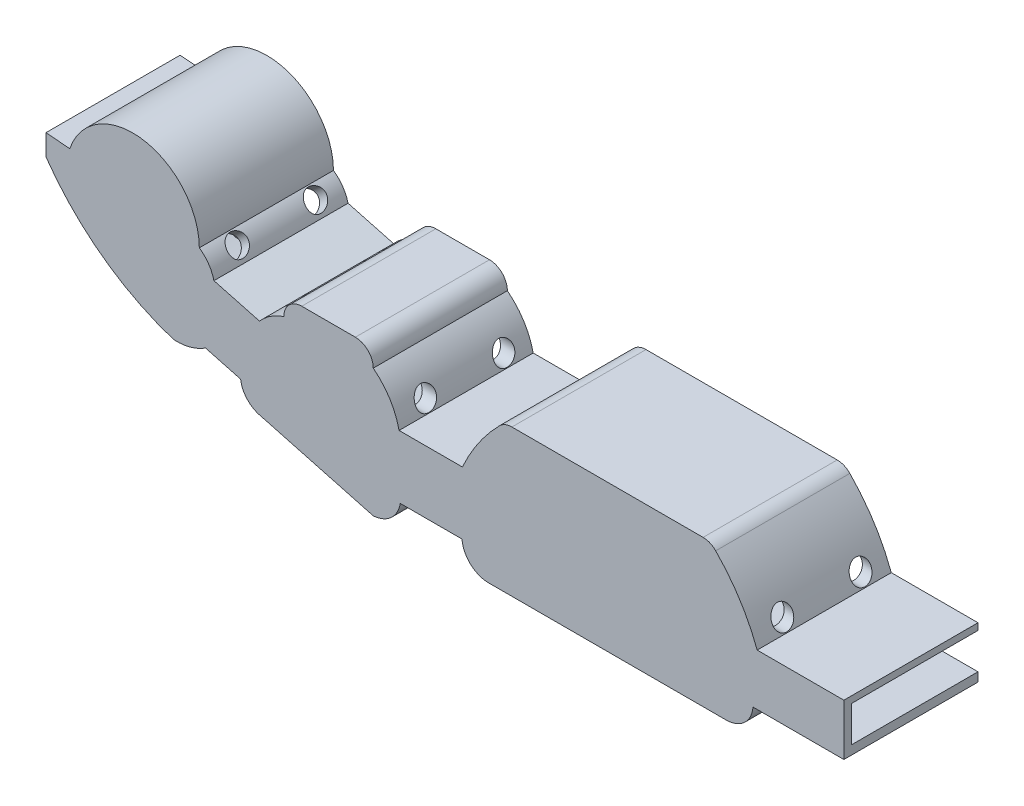
SolidWorks part; units mm, degrees
ref_plane "Front Plane" through (0, 0, 0) normal (0, 0, 1) x (1, 0, 0)
ref_plane "Top Plane" through (0, 0, 0) normal (0, 1, 0) x (1, 0, 0)
ref_plane "Right Plane" through (0, 0, 0) normal (1, 0, 0) x (0, 0, -1)
sketch "Sketch1" plane through (0, 0, 0) normal (0, 0, 1) x (1, 0, 0)
  line L5 (-97.6029, 12.3858) -> (-97.6029, 15.2174)
  line L6 (-97.6029, 15.2174) -> (-94.4145, 14.9459)
  line L10 (-35.074, 12.2681) -> (-9.4143, 12.2681)
  line L11 (-34.8319, 9.152) -> (-35.1352, 10.6577)
  line L13 (-93.5639, 9.2655) -> (-96.8614, 13.2092)
  line L14 (-96.8614, 13.2092) -> (-96.8614, 13.9453)
  line L17 (-96.8614, 13.9453) -> (-96.4758, 13.5047)
  line L19 (-51.77, 3.095) -> (-40.77, 3.095)
  line L20 (-40.7743, -2.905) -> (-51.8007, -2.905)
  line L21 (-63.3947, 10.6822) -> (-63.3108, 10.6822)
  line L22 (-67.3032, -2.5288) -> (-54.7475, -5.8983)
  line L23 (-11.1807, 10.652) -> (-11.4807, 9.152)
  line L24 (-11.4807, 9.152) -> (-11.7807, 10.652)
  line L25 (-11.7807, 10.652) -> (-12.4807, 10.652)
  line L30 (-94.818, 12.3858) -> (-96.4758, 13.5047)
  line L36 (-12.4807, 10.652) -> (-12.7807, 9.152)
  line L40 (-12.7807, 9.152) -> (-13.0807, 10.652)
  line L41 (-13.0807, 10.652) -> (-13.7547, 10.652)
  line L43 (-56.0812, 12.2025) -> (-63.2812, 12.2025)
  line L44 (-68.7563, -3.3191) -> (-53.6894, -7.3625)
  line L47 (-13.7547, 10.652) -> (-14.0547, 9.152)
  line L48 (-14.0547, 9.152) -> (-14.3547, 10.652)
  line L49 (-14.3547, 10.652) -> (-15.0547, 10.652)
  line L50 (-15.0547, 10.652) -> (-15.3547, 9.152)
  line L51 (-15.3547, 9.152) -> (-15.6547, 10.652)
  line L52 (-15.6547, 10.652) -> (-16.3547, 10.652)
  line L53 (-16.3547, 10.652) -> (-16.6547, 9.152)
  line L54 (-16.6547, 9.152) -> (-16.9547, 10.652)
  line L55 (-16.9547, 10.652) -> (-17.6547, 10.652)
  line L56 (-17.6547, 10.652) -> (-17.9547, 9.152)
  line L57 (-17.9547, 9.152) -> (-18.2547, 10.652)
  line L58 (-18.2547, 10.652) -> (-18.9547, 10.652)
  line L59 (-18.9547, 10.652) -> (-19.2547, 9.152)
  line L60 (-19.2547, 9.152) -> (-19.5547, 10.652)
  line L61 (-19.5547, 10.652) -> (-20.2547, 10.652)
  line L62 (-20.2547, 10.652) -> (-20.5547, 9.152)
  line L63 (-20.5547, 9.152) -> (-20.8547, 10.652)
  line L64 (-20.8547, 10.652) -> (-21.5547, 10.652)
  line L65 (-21.5547, 10.652) -> (-21.8547, 9.152)
  line L66 (-21.8547, 9.152) -> (-22.1547, 10.652)
  line L67 (-22.1547, 10.652) -> (-22.8547, 10.652)
  line L68 (-22.8547, 10.652) -> (-23.1547, 9.152)
  line L69 (-23.1547, 9.152) -> (-23.4547, 10.652)
  line L70 (-23.4547, 10.652) -> (-24.1547, 10.652)
  line L71 (-24.1547, 10.652) -> (-24.4547, 9.152)
  line L72 (-24.4547, 9.152) -> (-24.7547, 10.652)
  line L73 (-24.7547, 10.652) -> (-25.4547, 10.652)
  line L74 (-25.4547, 10.652) -> (-25.7547, 9.152)
  line L75 (-25.7547, 9.152) -> (-26.0547, 10.652)
  line L76 (-26.0547, 10.652) -> (-26.7547, 10.652)
  line L77 (-26.7547, 10.652) -> (-27.0547, 9.152)
  line L78 (-27.0547, 9.152) -> (-27.3547, 10.652)
  line L79 (-27.3547, 10.652) -> (-28.0547, 10.652)
  line L80 (-28.0547, 10.652) -> (-28.3547, 9.152)
  line L81 (-28.3547, 9.152) -> (-28.6547, 10.652)
  line L82 (-28.6547, 10.652) -> (-29.3547, 10.652)
  line L83 (-29.3547, 10.652) -> (-29.6547, 9.152)
  line L84 (-29.6547, 9.152) -> (-29.9547, 10.652)
  line L85 (-29.9547, 10.652) -> (-30.6547, 10.652)
  line L86 (-30.6547, 10.652) -> (-30.9547, 9.152)
  line L87 (-30.9547, 9.152) -> (-31.2547, 10.652)
  line L88 (-31.2547, 10.652) -> (-31.9547, 10.652)
  line L89 (-31.9547, 10.652) -> (-32.2547, 9.152)
  line L90 (-32.2547, 9.152) -> (-32.5547, 10.652)
  line L91 (-32.5547, 10.652) -> (-33.2547, 10.652)
  line L92 (-33.2547, 10.652) -> (-33.5547, 9.152)
  line L93 (-33.5547, 9.152) -> (-33.8547, 10.652)
  line L94 (-33.8547, 10.652) -> (-34.5287, 10.652)
  line L95 (-34.5287, 10.652) -> (-34.8319, 9.152)
  line L100 (-57.3947, 10.6822) -> (-57.5369, 10.6822)
  line L101 (-57.5369, 10.6822) -> (-57.8369, 9.1822)
  line L102 (-57.8369, 9.1822) -> (-58.1369, 10.6822)
  line L103 (-58.1369, 10.6822) -> (-58.8369, 10.6822)
  line L104 (-58.8369, 10.6822) -> (-59.1369, 9.1822)
  line L105 (-59.1369, 9.1822) -> (-59.4369, 10.6822)
  line L106 (-59.4369, 10.6822) -> (-60.1108, 10.6822)
  line L107 (-60.1108, 10.6822) -> (-60.4108, 9.1822)
  line L108 (-60.4108, 9.1822) -> (-60.7108, 10.6822)
  line L109 (-60.7108, 10.6822) -> (-61.4108, 10.6822)
  line L110 (-61.4108, 10.6822) -> (-61.7108, 9.1822)
  line L111 (-61.7108, 9.1822) -> (-62.0108, 10.6822)
  line L112 (-62.0108, 10.6822) -> (-62.7108, 10.6822)
  line L113 (-62.7108, 10.6822) -> (-63.0108, 9.1822)
  line L114 (-63.0108, 9.1822) -> (-63.3108, 10.6822)
  line L118 (-78.7208, 14.8576) -> (-79.0208, 12.8576)
  line L119 (-79.0208, 12.8576) -> (-79.3208, 15.955)
  line L120 (-80.0208, 16.8755) -> (-80.3208, 15.6755)
  line L121 (-80.3208, 15.6755) -> (-80.6208, 17.4876)
  line L122 (-81.3208, 18.0603) -> (-81.6208, 16.9603)
  line L123 (-81.6208, 16.9603) -> (-81.9208, 18.4574)
  line L124 (-82.6208, 18.8313) -> (-82.9208, 17.8313)
  line L125 (-82.9208, 17.8313) -> (-83.2208, 19.0854)
  line L126 (-83.9208, 19.313) -> (-84.2208, 18.263)
  line L127 (-84.2208, 18.263) -> (-84.5208, 19.4536)
  line L128 (-85.2208, 19.5578) -> (-85.5208, 18.4578)
  line L129 (-85.5208, 18.4578) -> (-85.8208, 19.5977)
  line L130 (-86.5221, 19.5875) -> (-86.8221, 18.3969)
  line L131 (-86.8221, 18.3969) -> (-87.1221, 19.5298)
  line L132 (-87.8199, 19.4048) -> (-88.1199, 18.1477)
  line L133 (-88.1199, 18.1477) -> (-88.4199, 19.2451)
  line L134 (-89.1193, 18.9938) -> (-89.4193, 17.6938)
  line L135 (-89.4193, 17.6938) -> (-89.7193, 18.7169)
  line L136 (-90.4175, 18.3139) -> (-90.7175, 16.8139)
  line L137 (-90.7175, 16.8139) -> (-91.0175, 17.886)
  line L138 (-91.719, 17.2662) -> (-92.019, 15.3662)
  line L139 (-92.019, 15.3662) -> (-92.319, 16.5999)
  line L148 (-68.9499, 7.6397) -> (-75.0624, 9.2801)
  line L156 (-73.89, 0.2682) -> (-76.1872, 0.8847)
  line L157 (-73.89, 0.2682) -> (-71.4824, -0.3779)
  line L161 (-76.2959, 8.3687) -> (-68.5693, 6.2951)
  line L162 (-77.4379, 2.4628) -> (-69.5973, 0.3587)
  line L163 (-50.0495, -4.105) -> (-41.7785, -4.105)
  line L164 (-50.2154, 4.295) -> (-41.7181, 4.295)
  line L165 (-37.7463, -6.2141) -> (-6.7463, -6.2141)
  line L166 (-38.1902, -7.4141) -> (-6.3025, -7.4141)
  line L167 (-22.2463, -6.2141) -> (-22.2463, -1.2141) construction
  line L168 (-40.77, 3.095) -> (-3.7183, 3.095) construction
  line L169 (-37.1454, 8.6822) -> (-3.7183, 8.6822) construction
  line L170 (-22.2442, 4.8532) -> (-22.2442, 21.169) construction
  line L171 (8.2817, 1.895) -> (-3.6348, 1.895)
  line L172 (-10.5067, 10.652) -> (-11.1807, 10.652)
  line L173 (-9.9067, 10.652) -> (-9.3532, 10.652)
  line L174 (-35.1352, 10.6577) -> (-35.1352, 4.8532) construction
  line L175 (-35.1352, 4.8532) -> (-9.3532, 4.8532) construction
  line L176 (-9.9067, 10.652) -> (-10.2067, 9.152)
  line L177 (-10.2067, 9.152) -> (-10.5067, 10.652)
  line L178 (-9.3532, 4.8532) -> (-9.3532, 10.652) construction
  line L179 (-3.7183, -2.905) -> (8.2817, -2.905)
  line L180 (-2.7142, -4.105) -> (9.4817, -4.105)
  line L183 (9.4817, 2.795) -> (9.4817, -4.105)
  line L184 (8.2817, 1.895) -> (8.2817, -2.905)
  line L185 (-2.1578, 2.795) -> (9.4817, 2.795)
  arc A2 (-93.5639, 9.2655) -> (-80.9402, 0.8179) centre (-72.8174, 26.6123) ccw
  arc A5 (-35.1352, 10.6577) -> (-36.661, 9.9746) centre (-35.1586, 8.6645) ccw
  arc A6 (-37.1454, 8.6822) -> (-40.77, 3.095) centre (-32.8748, 1.9424) ccw
  arc A8 (-36.661, 9.9746) -> (-37.1454, 8.6822) centre (-35.179, 8.6822) ccw
  arc A14 (-78.0208, 11.2299) -> (-78.7208, 14.8576) centre (-86.0539, 11.5612) ccw
  arc A15 (-79.3208, 15.955) -> (-80.0208, 16.8755) centre (-86.0539, 11.5612) ccw
  arc A16 (-80.6208, 17.4876) -> (-81.3208, 18.0603) centre (-86.0539, 11.5612) ccw
  arc A19 (-40.7743, -2.905) -> (-37.7463, -6.2141) centre (-37.7903, -3.2144) ccw
  arc A25 (-81.9208, 18.4574) -> (-82.6208, 18.8313) centre (-86.0539, 11.5612) ccw
  arc A26 (-54.7475, -5.8983) -> (-51.8007, -2.905) centre (-55.0595, -2.644) ccw
  arc A27 (-69.5973, 0.3587) -> (-67.3032, -2.5288) centre (-66.724, 0.2864) ccw
  arc A28 (-76.1872, 0.8847) -> (-80.4983, -0.2669) centre (-80.1184, 6.9561) cw
  arc A29 (-83.2208, 19.0854) -> (-83.9208, 19.313) centre (-86.0539, 11.5612) ccw
  arc A30 (-84.5208, 19.4536) -> (-85.2208, 19.5578) centre (-86.0539, 11.5612) ccw
  arc A31 (-41.7181, 4.295) -> (-36.7682, 11.551) centre (-19.1074, -5.8132) cw
  arc A33 (-85.8208, 19.5977) -> (-86.5221, 19.5875) centre (-86.0539, 11.5612) ccw
  arc A34 (-80.9402, 0.8179) -> (-77.4379, 2.4628) centre (-80.1638, 3.7157) ccw
  arc A37 (-76.2959, 8.3687) -> (-78.0208, 11.2299) centre (-80.3097, 7.8995) ccw
  arc A38 (-65.3947, 8.6822) -> (-68.5693, 6.2951) centre (-63.493, 2.8486) ccw
  arc A41 (-51.77, 3.095) -> (-55.3947, 8.6822) centre (-59.6652, 1.9424) ccw
  arc A42 (-55.3947, 8.6822) -> (-57.3947, 10.6822) centre (-57.3947, 8.6822) ccw
  arc A43 (-63.3947, 10.6822) -> (-65.3947, 8.6822) centre (-63.3947, 8.6822) ccw
  arc A45 (-94.0086, 12.7286) -> (-94.818, 12.3858) centre (-87.4925, -3.7856) ccw
  arc A47 (-35.074, 12.2681) -> (-36.7682, 11.551) centre (-35.074, 9.9085) ccw
  arc A48 (-87.1221, 19.5298) -> (-87.8199, 19.4048) centre (-86.0539, 11.5612) ccw
  arc A49 (-41.7785, -4.105) -> (-38.1902, -7.4141) centre (-38.1902, -3.8141) ccw
  arc A51 (-88.4199, 19.2451) -> (-89.1193, 18.9938) centre (-86.0539, 11.5612) ccw
  arc A52 (-89.7193, 18.7169) -> (-90.4175, 18.3139) centre (-86.0539, 11.5612) ccw
  arc A55 (-53.6894, -7.3625) -> (-50.0495, -4.105) centre (-53.9168, -3.446) ccw
  arc A56 (-71.4824, -0.3779) -> (-68.7563, -3.3191) centre (-68.0612, 0.0591) ccw
  arc A57 (-91.0175, 17.886) -> (-91.719, 17.2662) centre (-86.0539, 11.5612) ccw
  arc A58 (-97.6029, 12.3858) -> (-80.4983, -0.2669) centre (-70.1945, 31.5502) ccw
  arc A59 (-75.0624, 9.2801) -> (-77.0239, 12.1147) centre (-79.7705, 8.1183) ccw
  arc A60 (-65.6812, 9.8025) -> (-68.9499, 7.6397) centre (-63.3992, 2.8022) ccw
  arc A61 (-50.2154, 4.295) -> (-53.6812, 9.8025) centre (-59.5697, 2.2526) ccw
  arc A62 (-53.6812, 9.8025) -> (-56.0812, 12.2025) centre (-56.0812, 9.8025) ccw
  arc A63 (-63.2812, 12.2025) -> (-65.6812, 9.8025) centre (-63.2812, 9.8025) ccw
  arc A64 (-94.4145, 14.9459) -> (-77.0239, 12.1147) centre (-85.9551, 12.081) cw
  arc A65 (-92.319, 16.5999) -> (-94.0086, 12.7286) centre (-86.0539, 11.5612) ccw
  arc A66 (-2.7142, -4.105) -> (-6.3025, -7.4141) centre (-6.3025, -3.8141) cw
  arc A67 (-3.7183, -2.905) -> (-6.7463, -6.2141) centre (-6.7023, -3.2144) cw
  arc A69 (-7.343, 8.6822) -> (-9.3532, 10.652) centre (-10.3911, 7.5822) ccw
  arc A70 (-7.343, 8.6822) -> (-3.6348, 1.895) centre (-11.6135, 1.9424) cw
  arc A71 (-2.1578, 2.795) -> (-7.7202, 11.551) centre (-25.381, -5.8132) ccw
  arc A72 (-9.4143, 12.2681) -> (-7.7202, 11.551) centre (-9.4143, 9.9085) cw
  point P92 (-21.3666, 12.2681)
  dimension "D1" = 6
  dimension "D4" = 6
  dimension "D2" = 1.2
  dimension "D3" = 1.2
  dimension "D5" = 1.2
  dimension "D6" = 1.2
  dimension "D7" = 1.2
  dimension "D8" = 11
  dimension "D9" = 8
  dimension "D10" = 18.0933
  dimension "D11" = 20.0133
  dimension "D12" = 31
  dimension "D13" = 3.6247
  dimension "D14" = 12
  dimension "D15" = 5
  dimension "D16" = 5.6348
  dimension "D17" = 5.6348
  dimension "D18" = 4.8
  dimension "D19" = 6.9
  dimension "D20" = 11.9164
  dimension "D21" = 11.0264
  dimension "D22" = 8.1181
extrude "Walls" add sketch "Sketch1" along normal blind 16 contours A59 A64 L6 L5 A58 A28 A56 L44 A55 A49 L10 A47 A31 A61 A62 L43 A63 A60 A45 A37 A38 A43 A42 A41 L19 A6 region at (-96.495, 13.8016, 0)
sketch "Sketch2" plane through (0, 0, 0) normal (0, 0, -1) x (-1, 0, 0)
  line L10 (75.0624, 9.2801) -> (68.9499, 7.6397)
  line L11 (75.0624, 9.2801) -> (68.9499, 7.6397)
  line L12 (71.4824, -0.3779) -> (76.1872, 0.8847)
  line L13 (71.4824, -0.3779) -> (76.1872, 0.8847)
  line L14 (63.2812, 12.2025) -> (56.0812, 12.2025)
  line L15 (2.1578, 2.795) -> (-9.4817, 2.795)
  line L16 (35.074, 12.2681) -> (9.4143, 12.2681)
  line L17 (2.1578, 2.795) -> (-9.4817, 2.795)
  line L18 (-9.4817, 2.795) -> (-9.4817, -4.105)
  line L19 (53.6894, -7.3625) -> (68.7563, -3.3191)
  line L22 (97.6029, 12.3858) -> (97.6029, 15.2174)
  line L23 (97.6029, 15.2174) -> (94.4145, 14.9459)
  line L26 (63.2812, 12.2025) -> (56.0812, 12.2025)
  line L28 (35.074, 12.2681) -> (9.4143, 12.2681)
  line L31 (53.6894, -7.3625) -> (68.7563, -3.3191)
  line L34 (97.6029, 12.3858) -> (97.6029, 15.2174)
  line L35 (97.6029, 15.2174) -> (94.4145, 14.9459)
  line L37 (-9.4817, 2.795) -> (-9.4817, -4.105)
  line L38 (-9.4817, -4.105) -> (2.7142, -4.105)
  line L39 (-9.4817, -4.105) -> (2.7142, -4.105)
  line L40 (6.3025, -7.4141) -> (38.1902, -7.4141)
  line L41 (6.3025, -7.4141) -> (38.1902, -7.4141)
  line L42 (41.7785, -4.105) -> (50.0495, -4.105)
  line L43 (41.7785, -4.105) -> (50.0495, -4.105)
  line L44 (50.2154, 4.295) -> (41.7181, 4.295)
  line L45 (50.2154, 4.295) -> (41.7181, 4.295)
  arc A16 (9.4143, 12.2681) -> (7.7202, 11.551) centre (9.4143, 9.9085) ccw
  arc A17 (9.4143, 12.2681) -> (7.7202, 11.551) centre (9.4143, 9.9085) ccw
  arc A18 (77.0239, 12.1147) -> (75.0624, 9.2801) centre (79.7705, 8.1183) ccw
  arc A19 (68.9499, 7.6397) -> (65.6812, 9.8025) centre (63.3992, 2.8022) ccw
  arc A20 (65.6812, 9.8025) -> (63.2812, 12.2025) centre (63.2812, 9.8025) ccw
  arc A21 (56.0812, 12.2025) -> (53.6812, 9.8025) centre (56.0812, 9.8025) ccw
  arc A22 (53.6812, 9.8025) -> (50.2154, 4.295) centre (59.5697, 2.2526) ccw
  arc A23 (41.7181, 4.295) -> (36.7682, 11.551) centre (19.1074, -5.8132) ccw
  arc A24 (36.7682, 11.551) -> (35.074, 12.2681) centre (35.074, 9.9085) ccw
  arc A25 (7.7202, 11.551) -> (2.1578, 2.795) centre (25.381, -5.8132) ccw
  arc A26 (7.7202, 11.551) -> (2.1578, 2.795) centre (25.381, -5.8132) ccw
  arc A27 (2.7142, -4.105) -> (6.3025, -7.4141) centre (6.3025, -3.8141) ccw
  arc A28 (2.7142, -4.105) -> (6.3025, -7.4141) centre (6.3025, -3.8141) ccw
  arc A30 (38.1902, -7.4141) -> (41.7785, -4.105) centre (38.1902, -3.8141) ccw
  arc A31 (50.0495, -4.105) -> (53.6894, -7.3625) centre (53.9168, -3.446) ccw
  arc A32 (68.7563, -3.3191) -> (71.4824, -0.3779) centre (68.0612, 0.0591) ccw
  arc A33 (76.1872, 0.8847) -> (80.4983, -0.2669) centre (80.1184, 6.9561) ccw
  arc A34 (80.4983, -0.2669) -> (97.6029, 12.3858) centre (70.1945, 31.5502) ccw
  arc A35 (94.4145, 14.9459) -> (77.0239, 12.1147) centre (85.9551, 12.081) ccw
  arc A36 (77.0239, 12.1147) -> (75.0624, 9.2801) centre (79.7705, 8.1183) ccw
  arc A37 (68.9499, 7.6397) -> (65.6812, 9.8025) centre (63.3992, 2.8022) ccw
  arc A38 (65.6812, 9.8025) -> (63.2812, 12.2025) centre (63.2812, 9.8025) ccw
  arc A39 (56.0812, 12.2025) -> (53.6812, 9.8025) centre (56.0812, 9.8025) ccw
  arc A40 (53.6812, 9.8025) -> (50.2154, 4.295) centre (59.5697, 2.2526) ccw
  arc A41 (41.7181, 4.295) -> (36.7682, 11.551) centre (19.1074, -5.8132) ccw
  arc A42 (36.7682, 11.551) -> (35.074, 12.2681) centre (35.074, 9.9085) ccw
  arc A48 (38.1902, -7.4141) -> (41.7785, -4.105) centre (38.1902, -3.8141) ccw
  arc A49 (50.0495, -4.105) -> (53.6894, -7.3625) centre (53.9168, -3.446) ccw
  arc A50 (68.7563, -3.3191) -> (71.4824, -0.3779) centre (68.0612, 0.0591) ccw
  arc A51 (76.1872, 0.8847) -> (80.4983, -0.2669) centre (80.1184, 6.9561) ccw
  arc A52 (80.4983, -0.2669) -> (97.6029, 12.3858) centre (70.1945, 31.5502) ccw
  arc A53 (94.4145, 14.9459) -> (77.0239, 12.1147) centre (85.9551, 12.081) ccw
  dimension "D1" = 0
extrude "Base" add sketch "Sketch2" along normal blind 1
sketch "Sketch3" [suppressed] plane through (0, 0, 0) normal (0, 0, 1) x (1, 0, 0)
  line L4 (-65.1711, 5.3832) -> (-63.3958, 4.9067) construction
  line L5 (-84.8697, 19.5134) -> (-85.1843, 17.3997) construction
  line L6 (-51.77, 3.095) -> (-68.5693, 3.095) construction
  line L7 (-68.5693, 6.2951) -> (-68.5693, 3.095) construction
  line L8 (-51.77, 3.095) -> (-54.6697, 3.095) construction
  line L9 (-68.5693, 6.2951) -> (-65.1711, 5.3832) construction
  line L10 (-56.4697, 3.095) -> (-54.6697, 3.095) construction
  line L11 (-80.595, 9.5224) -> (-82.2789, 9.9743)
  line L12 (-80.595, 9.5224) -> (-76.2959, 8.3687) construction
  line L13 (-91.8537, 12.2226) -> (-90.116, 11.8146)
  line L14 (-82.2789, 9.9743) -> (-90.116, 11.8146) construction
  line L15 (-40.77, 3.095) -> (-37.27, 3.095) construction
  line L16 (-3.6422, 1.595) -> (-7.1422, 1.595) construction
  line L17 (-40.77, 3.095) -> (-3.7183, 3.095) construction
  line L18 (-22.2442, 8.652) -> (-22.2442, 3.095) construction
  line L19 (-22.8547, 10.652) -> (-22.1547, 10.652) construction
  line L20 (-22.2442, 10.652) -> (-22.2442, 8.652) construction
  line L21 (-37.27, 3.095) -> (-34.1769, 3.095) construction
  line L22 (-11.7175, 3.095) -> (-7.1422, 1.595) construction
  arc A1 (-82.2789, 9.9743) -> (-90.116, 11.8146) centre (-86.0365, 11.58) ccw
  arc A2 (-91.8537, 12.2226) -> (-80.595, 9.5224) centre (-86.0443, 11.6231) cw
  arc A3 (-54.6697, 3.095) -> (-65.1711, 5.3832) centre (-60.1697, 3.095) ccw construction
  arc A4 (-84.5208, 19.4536) -> (-85.2208, 19.5578) centre (-86.0539, 11.5612) ccw construction
  arc A5 (-56.4697, 3.095) -> (-63.3958, 4.9067) centre (-60.1697, 3.095) ccw construction
  arc A6 (-3.6422, 1.595) -> (-7.343, 8.6822) centre (-11.6135, 1.9424) ccw construction
  arc A7 (-7.1422, 1.595) -> (-37.27, 3.095) centre (-22.9472, -12.5401) ccw construction
  arc A8 (-11.7175, 3.095) -> (-34.1769, 3.095) centre (-22.9472, -12.5401) ccw construction
  dimension "D1" = 11
  dimension "D2" = 2.137
  dimension "D3" = 7.4
  dimension "D8" = 38.5
  dimension "D4" = 3.5184
  dimension "D5" = 3.5
  dimension "D6" = 3.5
  dimension "D7" = 2
sketch "Sketch4" [suppressed] plane through (0, 0, 16) normal (0, 0, 1) x (1, 0, 0)
  line L7 (-69.5947, 0.3005) -> (-71.4824, -0.3779)
  line L10 (-71.4824, -0.3779) -> (-76.1872, 0.8847)
  line L11 (-76.1872, 0.8847) -> (-77.6773, 2.0433)
  line L12 (-40.77, 3.095) -> (-41.1043, 4.1128)
  line L13 (-41.1043, 4.1128) -> (-49.5364, 4.1128)
  line L16 (-67.7226, 6.3478) -> (-68.9499, 7.6397)
  line L17 (-68.9499, 7.6397) -> (-75.0624, 9.2801)
  line L18 (-75.0624, 9.2801) -> (-76.3177, 7.7352)
  line L19 (-49.5364, 4.1128) -> (-51.77, 3.095)
  line L20 (-40.7743, -2.905) -> (-41.0926, -4.1129)
  line L21 (-41.0926, -4.1129) -> (-49.3636, -4.1129)
  line L22 (-49.3636, -4.1129) -> (-51.8007, -2.905)
  arc A0 (-67.7226, 6.3478) -> (-76.3177, 7.7352) centre (-69.7742, 20.955) cw
  arc A1 (-69.5947, 0.3005) -> (-77.6773, 2.0433) centre (-76.3689, -11.5028) ccw
  arc A2 (-40.7743, -2.905) -> (-51.8007, -2.905) centre (-46.2875, -28.5004) ccw
  arc A3 (-40.77, 3.095) -> (-51.77, 3.095) centre (-46.27, 28.5687) cw
extrude "Joint Width" [suppressed] add sketch "Sketch4" against normal blind 16
ref_plane "SideAnchorPlane" through (0, 0, 2.5) normal (0, 0, 1) x (1, 0, 0)
ref_plane "CentralAnchorPlane" through (0, 0, 13) normal (0, 0, 1) x (1, 0, 0)
sketch "Sketch5" [suppressed] plane through (0, 0, 3) normal (0, 0, 1) x (1, 0, 0)
  line L0 (-76.2959, 8.3687) -> (-68.5693, 6.2951) construction
  line L1 (-76.592, 9.4835) -> (-67.8744, 7.144) construction
  line L2 (-77.4258, 10.7304) -> (-66.9487, 7.9187) construction
  line L3 (-76.592, 9.4835) -> (-88.7757, 4.7797)
  line L4 (-77.4258, 10.7304) -> (-90.1205, 5.8293)
  line L5 (-78.0158, 11.7317) -> (-91.096, 6.6818)
  line L6 (-76.2959, 8.3687) -> (-87.6359, 3.9906)
  line L7 (-78.0158, 11.7317) -> (-77.4258, 10.7304)
  line L9 (-76.592, 9.4835) -> (-76.0479, 8.9395)
  line L10 (-76.0479, 8.9395) -> (-76.2959, 8.3687)
  line L11 (-91.096, 6.6818) -> (-91.096, 6.0024)
  line L12 (-91.096, 6.0024) -> (-90.1205, 5.8293)
  line L13 (-88.7757, 4.7797) -> (-88.5883, 3.9906)
  line L14 (-88.5883, 3.9906) -> (-87.6359, 3.9906)
  arc A0 (-76.2959, 8.3687) -> (-78.0208, 11.2299) centre (-80.3097, 7.8995) ccw construction
  arc A1 (-65.3947, 8.6822) -> (-68.5693, 6.2951) centre (-63.493, 2.8486) ccw construction
  arc A2 (-76.2959, 8.3687) -> (-78.0208, 11.2299) centre (-80.3097, 7.8995) ccw construction
  arc A4 (-93.5639, 9.2655) -> (-80.9402, 0.8179) centre (-72.8174, 26.6123) ccw construction
  arc A5 (-93.5639, 9.2655) -> (-80.9402, 0.8179) centre (-72.8174, 26.6123) ccw construction
  dimension "D1" = 1
  dimension "D2" = 1.5
  dimension "D3" = 1.1466
  dimension "D4" = 1.1466
extrude "Boss-Extrude2" [suppressed] add sketch "Sketch5" along normal blind 1 and the other way blind 1 separate body
sketch "Sketch6" [suppressed] plane through (0, 0, 4) normal (0, 0, 1) x (1, 0, 0)
  line L1 (-87.6359, 3.9906) -> (-76.2959, 8.3687)
  line L4 (-78.0158, 11.7317) -> (-91.096, 6.6818)
  line L5 (-91.096, 6.6818) -> (-91.7792, 6.284)
  line L6 (-91.7792, 6.284) -> (-88.4163, 3.7031)
  line L7 (-88.4163, 3.7031) -> (-87.6359, 3.9906)
  line L8 (-78.0158, 11.7317) -> (-75.9969, 10.8669)
  line L9 (-75.9969, 10.8669) -> (-76.2959, 8.3687)
  arc A0 (-93.5639, 9.2655) -> (-80.9402, 0.8179) centre (-72.8174, 26.6123) ccw construction
extrude "Boss-Extrude4" [suppressed] add sketch "Sketch6" along normal blind 1
sketch "Sketch7" [suppressed] plane through (0, 0, 2) normal (0, 0, -1) x (-1, 0, 0)
  line L0 (87.6359, 3.9906) -> (90.1015, 4.9746)
  line L1 (90.1015, 4.9746) -> (91.096, 6.6818)
  line L2 (91.096, 6.6818) -> (78.0158, 11.7317)
  line L3 (78.0158, 11.7317) -> (76.2959, 10.4542)
  line L4 (76.2959, 10.4542) -> (76.2959, 8.3687)
  line L5 (76.2959, 8.3687) -> (87.6359, 3.9906)
extrude "Boss-Extrude5" [suppressed] add sketch "Sketch7" along normal blind 1
extrude "Boss-Extrude6" [suppressed] add sketch "Sketch3" along normal up to surface (16 mm away)
sketch "Sketch8" plane through (0, 0, 2.5) normal (0, 0, 1) x (1, 0, 0)
  line L2 (-75.9174, 11.0626) -> (-66.0659, 8.4188) construction
  line L5 (-52.6781, 5.795) -> (-39.8619, 5.795) construction
  line L7 (-3.9894, 4.295) -> (11.6619, 4.295) construction
  line L121 (-77.8002, 11.067) -> (-76.41, 8.9592)
  line L122 (-76.7997, 11.9511) -> (-75.2827, 11.509)
  line L123 (-75.2827, 11.509) -> (-75.2827, 9.9554)
  line L124 (-75.9174, 11.0626) -> (-72.3901, 7.0708) construction
  line L138 (-66.0659, 8.4188) -> (-52.6781, 5.795) construction
  line L139 (-39.8619, 5.795) -> (-3.9894, 4.295) construction
  line L140 (-75.9174, 11.0626) -> (-76.9521, 10.1483) construction
  line L142 (-76.7997, 11.9511) -> (-77.8002, 11.067)
  line L144 (-75.2827, 9.9554) -> (-76.41, 8.9592)
  arc A2 (-75.0624, 9.2801) -> (-77.0239, 12.1147) centre (-79.7705, 8.1183) ccw construction
  circle A48 centre (-76.4347, 10.6055) radius 1.25 construction
  dimension "D22" = 2.5
ref_plane "Plane3" through (-55, 0, 0) normal (1, 0, 0) x (0, 0, -1)
sketch "Sketch14" plane through (-55, 0, 0) normal (1, 0, 0) x (0, 0, -1)
  line L0 (-13, 0.165) -> (-13, -0.165) construction
  line L1 (-2.5, 0.165) -> (-2.5, -0.165) construction
  line L2 (-16, 3.095) -> (0, 3.095) construction
  line L3 (-16, 3.095) -> (0, 3.095) construction
  line L4 (0, 3.095) -> (0, 8.4472) construction
  line L5 (0, 8.6822) -> (0, 3.095) construction
  line L6 (0, 8.4472) -> (-16, 8.4472) construction
  line L7 (-16, 8.6822) -> (-16, 3.095) construction
  line L8 (-16, 8.4472) -> (-16, 3.095) construction
  line L9 (0, 5.7711) -> (-16, 5.7711) construction
  circle A0 centre (-13, 5.7711) radius 1.4
  circle A1 centre (-2.5, 5.7711) radius 1.4
  dimension "D1" = 2.8
  dimension "D2" = 2.8
  dimension "D3" = 2.6761
  dimension "D4" = 2.6761
extrude "Cut-Extrude2" cut sketch "Sketch14" along normal up to surface (15.1249 mm away) up to face at (-39.2631, 6.0868, 8)
sketch "Sketch15" plane through (0, 0, 0) normal (1, 0, 0) x (0, 0, -1)
  line L0 (-16, 2.795) -> (1, 2.795) construction
  line L1 (-13, 2.795) -> (-13, 4.295) construction
  line L2 (-13, 14.1985) -> (-13, -14.1985) construction
  line L3 (-13, 4.295) -> (-2.5, 4.295) construction
  line L4 (-2.5, 5.795) -> (-2.5, 4.295) construction
  circle A0 centre (-13, 4.295) radius 1.4
  circle A1 centre (-2.5, 4.295) radius 1.4
  dimension "D2" = 2.8
  dimension "D1" = 1.5
extrude "Cut-Extrude3" cut sketch "Sketch15" against normal up to surface (3.9894 mm away) up to face at (-5.0502, 5.5283, 8)
ref_plane "Plane4" through (-39.5082, -33.1252, 0) normal (0.7663, 0.6425, 0) x (0, 0, -1)
sketch "Sketch16" plane through (-39.5082, -33.1252, 0) normal (0.7663, 0.6425, 0) x (0, 0, -1)
  line L0 (-2.5, 58.4664) -> (-2.5, 55.9581) construction
  line L1 (-2.5, 57.2123) -> (-13, 57.2123) construction
  line L2 (-13, 14.1985) -> (-13, -14.1985) construction
  line L3 (-16, 58.7705) -> (-16, 55.4322) construction
  line L4 (-16, 55.4322) -> (1, 55.4322) construction
  line L5 (1, 55.3382) -> (1, 58.7705) construction
  line L6 (1, 55.4322) -> (1, 58.7705) construction
  circle A0 centre (-2.5, 57.2123) radius 1.4
  circle A1 centre (-13, 57.2123) radius 1.4
  dimension "D1" = 2.8
  dimension "D2" = 3
extrude "Cut-Extrude4" cut sketch "Sketch16" against normal up to surface and the other way up to surface up to face at (-89.5671, 5.3613, 7.5) other way up to face at (-75.913, 10.7875, 7.5)
ref_plane "Plane5" through (-63.3247, 23.0762, 0) normal (-0.9396, 0.3424, 0) x (0, 0, -1)
sketch "Sketch18" plane through (-63.3247, 23.0762, 0) normal (-0.9396, 0.3424, 0) x (0, 0, -1)
  line L0 (-13, 14.8654) -> (-2.5, 14.8554) construction
  line L2 (-2.5, 14.71) -> (-2.5, 12.5914) construction
  line L3 (-2.5, 13.2814) -> (-13, 13.2814) construction
  line L4 (-13, 14.1985) -> (-13, -14.1985) construction
  line L8 (-13, 13.2814) -> (-13, 16.4494) construction
  line L9 (-13, 16.4494) -> (-2.5, 16.4294) construction
  line L10 (-2.5, 15.599) -> (-2.5, 18.1418) construction
  line L11 (-16, 16.4294) -> (1, 16.4294) construction
  line L12 (-2.5, 16.4294) -> (-2.5, 13.2814) construction
  circle A0 centre (-2.5, 14.8554) radius 1.4
  circle A1 centre (-13, 14.8654) radius 1.4
  dimension "D1" = 2.8
extrude "Cut-Extrude5" cut sketch "Sketch18" against normal up to surface (1.3116 mm away) up to face at (-67.0813, 7.6207, 8)
sketch "Sketch19" plane through (0, 0, 0) normal (0, 0, 1) x (1, 0, 0)
  line L3 (-34.8319, 9.152) -> (-35.1352, 10.6577)
  line L4 (-93.5639, 9.2655) -> (-96.8614, 13.2092)
  line L5 (-96.8614, 13.2092) -> (-96.8614, 13.9453)
  line L6 (-96.8614, 13.9453) -> (-96.4758, 13.5047)
  line L7 (-51.77, 3.095) -> (-40.77, 3.095)
  line L8 (-40.7743, -2.905) -> (-51.8007, -2.905)
  line L9 (-63.3947, 10.6822) -> (-63.3108, 10.6822)
  line L10 (-67.3032, -2.5288) -> (-54.7475, -5.8983)
  line L11 (-11.1807, 10.652) -> (-11.4807, 9.152)
  line L12 (-11.4807, 9.152) -> (-11.7807, 10.652)
  line L13 (-11.7807, 10.652) -> (-12.4807, 10.652)
  line L14 (-94.818, 12.3858) -> (-96.4758, 13.5047)
  line L15 (-12.4807, 10.652) -> (-12.7807, 9.152)
  line L16 (-12.7807, 9.152) -> (-13.0807, 10.652)
  line L17 (-13.0807, 10.652) -> (-13.7547, 10.652)
  line L20 (-13.7547, 10.652) -> (-14.0547, 9.152)
  line L21 (-14.0547, 9.152) -> (-14.3547, 10.652)
  line L22 (-14.3547, 10.652) -> (-15.0547, 10.652)
  line L23 (-15.0547, 10.652) -> (-15.3547, 9.152)
  line L24 (-15.3547, 9.152) -> (-15.6547, 10.652)
  line L25 (-15.6547, 10.652) -> (-16.3547, 10.652)
  line L26 (-16.3547, 10.652) -> (-16.6547, 9.152)
  line L27 (-16.6547, 9.152) -> (-16.9547, 10.652)
  line L28 (-16.9547, 10.652) -> (-17.6547, 10.652)
  line L29 (-17.6547, 10.652) -> (-17.9547, 9.152)
  line L30 (-17.9547, 9.152) -> (-18.2547, 10.652)
  line L31 (-18.2547, 10.652) -> (-18.9547, 10.652)
  line L32 (-18.9547, 10.652) -> (-19.2547, 9.152)
  line L33 (-19.2547, 9.152) -> (-19.5547, 10.652)
  line L34 (-19.5547, 10.652) -> (-20.2547, 10.652)
  line L35 (-20.2547, 10.652) -> (-20.5547, 9.152)
  line L36 (-20.5547, 9.152) -> (-20.8547, 10.652)
  line L37 (-20.8547, 10.652) -> (-21.5547, 10.652)
  line L38 (-21.5547, 10.652) -> (-21.8547, 9.152)
  line L39 (-21.8547, 9.152) -> (-22.1547, 10.652)
  line L40 (-22.1547, 10.652) -> (-22.8547, 10.652)
  line L41 (-22.8547, 10.652) -> (-23.1547, 9.152)
  line L42 (-23.1547, 9.152) -> (-23.4547, 10.652)
  line L43 (-23.4547, 10.652) -> (-24.1547, 10.652)
  line L44 (-24.1547, 10.652) -> (-24.4547, 9.152)
  line L45 (-24.4547, 9.152) -> (-24.7547, 10.652)
  line L46 (-24.7547, 10.652) -> (-25.4547, 10.652)
  line L47 (-25.4547, 10.652) -> (-25.7547, 9.152)
  line L48 (-25.7547, 9.152) -> (-26.0547, 10.652)
  line L49 (-26.0547, 10.652) -> (-26.7547, 10.652)
  line L50 (-26.7547, 10.652) -> (-27.0547, 9.152)
  line L51 (-27.0547, 9.152) -> (-27.3547, 10.652)
  line L52 (-27.3547, 10.652) -> (-28.0547, 10.652)
  line L53 (-28.0547, 10.652) -> (-28.3547, 9.152)
  line L54 (-28.3547, 9.152) -> (-28.6547, 10.652)
  line L55 (-28.6547, 10.652) -> (-29.3547, 10.652)
  line L56 (-29.3547, 10.652) -> (-29.6547, 9.152)
  line L57 (-29.6547, 9.152) -> (-29.9547, 10.652)
  line L58 (-29.9547, 10.652) -> (-30.6547, 10.652)
  line L59 (-30.6547, 10.652) -> (-30.9547, 9.152)
  line L60 (-30.9547, 9.152) -> (-31.2547, 10.652)
  line L61 (-31.2547, 10.652) -> (-31.9547, 10.652)
  line L62 (-31.9547, 10.652) -> (-32.2547, 9.152)
  line L63 (-32.2547, 9.152) -> (-32.5547, 10.652)
  line L64 (-32.5547, 10.652) -> (-33.2547, 10.652)
  line L65 (-33.2547, 10.652) -> (-33.5547, 9.152)
  line L66 (-33.5547, 9.152) -> (-33.8547, 10.652)
  line L67 (-33.8547, 10.652) -> (-34.5287, 10.652)
  line L68 (-34.5287, 10.652) -> (-34.8319, 9.152)
  line L69 (-57.3947, 10.6822) -> (-57.5369, 10.6822)
  line L70 (-57.5369, 10.6822) -> (-57.8369, 9.1822)
  line L71 (-57.8369, 9.1822) -> (-58.1369, 10.6822)
  line L72 (-58.1369, 10.6822) -> (-58.8369, 10.6822)
  line L73 (-58.8369, 10.6822) -> (-59.1369, 9.1822)
  line L74 (-59.1369, 9.1822) -> (-59.4369, 10.6822)
  line L75 (-59.4369, 10.6822) -> (-60.1108, 10.6822)
  line L76 (-60.1108, 10.6822) -> (-60.4108, 9.1822)
  line L77 (-60.4108, 9.1822) -> (-60.7108, 10.6822)
  line L78 (-60.7108, 10.6822) -> (-61.4108, 10.6822)
  line L79 (-61.4108, 10.6822) -> (-61.7108, 9.1822)
  line L80 (-61.7108, 9.1822) -> (-62.0108, 10.6822)
  line L81 (-62.0108, 10.6822) -> (-62.7108, 10.6822)
  line L82 (-62.7108, 10.6822) -> (-63.0108, 9.1822)
  line L83 (-63.0108, 9.1822) -> (-63.3108, 10.6822)
  line L84 (-78.7208, 14.8576) -> (-79.0208, 12.8576)
  line L85 (-79.0208, 12.8576) -> (-79.3208, 15.955)
  line L86 (-80.0208, 16.8755) -> (-80.3208, 15.6755)
  line L87 (-80.3208, 15.6755) -> (-80.6208, 17.4876)
  line L88 (-81.3208, 18.0603) -> (-81.6208, 16.9603)
  line L89 (-81.6208, 16.9603) -> (-81.9208, 18.4574)
  line L90 (-82.6208, 18.8313) -> (-82.9208, 17.8313)
  line L91 (-82.9208, 17.8313) -> (-83.2208, 19.0854)
  line L92 (-83.9208, 19.313) -> (-84.2208, 18.263)
  line L93 (-84.2208, 18.263) -> (-84.5208, 19.4536)
  line L94 (-85.2208, 19.5578) -> (-85.5208, 18.4578)
  line L95 (-85.5208, 18.4578) -> (-85.8208, 19.5977)
  line L96 (-86.5221, 19.5875) -> (-86.8221, 18.3969)
  line L97 (-86.8221, 18.3969) -> (-87.1221, 19.5298)
  line L98 (-87.8199, 19.4048) -> (-88.1199, 18.1477)
  line L99 (-88.1199, 18.1477) -> (-88.4199, 19.2451)
  line L100 (-89.1193, 18.9938) -> (-89.4193, 17.6938)
  line L101 (-89.4193, 17.6938) -> (-89.7193, 18.7169)
  line L102 (-90.4175, 18.3139) -> (-90.7175, 16.8139)
  line L103 (-90.7175, 16.8139) -> (-91.0175, 17.886)
  line L104 (-91.719, 17.2662) -> (-92.019, 15.3662)
  line L105 (-92.019, 15.3662) -> (-92.319, 16.5999)
  line L109 (-76.2959, 8.3687) -> (-68.5693, 6.2951)
  line L110 (-77.4379, 2.4628) -> (-69.5973, 0.3587)
  line L113 (-37.7463, -6.2141) -> (-6.7463, -6.2141)
  line L115 (-22.2463, -6.2141) -> (-22.2463, -1.2141) construction
  line L116 (-40.77, 3.095) -> (-3.7183, 3.095) construction
  line L117 (-37.1454, 8.6822) -> (-3.7183, 8.6822) construction
  line L118 (-22.2442, 4.8532) -> (-22.2442, 21.169) construction
  line L119 (8.2817, 1.895) -> (-3.6348, 1.895)
  line L120 (-10.5067, 10.652) -> (-11.1807, 10.652)
  line L121 (-9.9067, 10.652) -> (-9.3532, 10.652)
  line L122 (-35.1352, 10.6577) -> (-35.1352, 4.8532) construction
  line L123 (-35.1352, 4.8532) -> (-9.3532, 4.8532) construction
  line L124 (-9.9067, 10.652) -> (-10.2067, 9.152)
  line L125 (-10.2067, 9.152) -> (-10.5067, 10.652)
  line L126 (-9.3532, 4.8532) -> (-9.3532, 10.652) construction
  line L127 (-3.7183, -2.905) -> (8.2817, -2.905)
  line L130 (8.2817, 1.895) -> (8.2817, -2.905)
  arc A0 (-93.5639, 9.2655) -> (-80.9402, 0.8179) centre (-72.8174, 26.6123) ccw
  arc A1 (-35.1352, 10.6577) -> (-36.661, 9.9746) centre (-35.1586, 8.6645) ccw
  arc A2 (-37.1454, 8.6822) -> (-40.77, 3.095) centre (-32.8748, 1.9424) ccw
  arc A3 (-36.661, 9.9746) -> (-37.1454, 8.6822) centre (-35.179, 8.6822) ccw
  arc A4 (-78.0208, 11.2299) -> (-78.7208, 14.8576) centre (-86.0539, 11.5612) ccw
  arc A5 (-79.3208, 15.955) -> (-80.0208, 16.8755) centre (-86.0539, 11.5612) ccw
  arc A6 (-80.6208, 17.4876) -> (-81.3208, 18.0603) centre (-86.0539, 11.5612) ccw
  arc A7 (-40.7743, -2.905) -> (-37.7463, -6.2141) centre (-37.7903, -3.2144) ccw
  arc A8 (-81.9208, 18.4574) -> (-82.6208, 18.8313) centre (-86.0539, 11.5612) ccw
  arc A9 (-54.7475, -5.8983) -> (-51.8007, -2.905) centre (-55.0595, -2.644) ccw
  arc A10 (-69.5973, 0.3587) -> (-67.3032, -2.5288) centre (-66.724, 0.2864) ccw
  arc A12 (-83.2208, 19.0854) -> (-83.9208, 19.313) centre (-86.0539, 11.5612) ccw
  arc A13 (-84.5208, 19.4536) -> (-85.2208, 19.5578) centre (-86.0539, 11.5612) ccw
  arc A15 (-85.8208, 19.5977) -> (-86.5221, 19.5875) centre (-86.0539, 11.5612) ccw
  arc A16 (-80.9402, 0.8179) -> (-77.4379, 2.4628) centre (-80.1638, 3.7157) ccw
  arc A17 (-76.2959, 8.3687) -> (-78.0208, 11.2299) centre (-80.3097, 7.8995) ccw
  arc A18 (-65.3947, 8.6822) -> (-68.5693, 6.2951) centre (-63.493, 2.8486) ccw
  arc A19 (-51.77, 3.095) -> (-55.3947, 8.6822) centre (-59.6652, 1.9424) ccw
  arc A20 (-55.3947, 8.6822) -> (-57.3947, 10.6822) centre (-57.3947, 8.6822) ccw
  arc A21 (-63.3947, 10.6822) -> (-65.3947, 8.6822) centre (-63.3947, 8.6822) ccw
  arc A22 (-94.0086, 12.7286) -> (-94.818, 12.3858) centre (-87.4925, -3.7856) ccw
  arc A24 (-87.1221, 19.5298) -> (-87.8199, 19.4048) centre (-86.0539, 11.5612) ccw
  arc A26 (-88.4199, 19.2451) -> (-89.1193, 18.9938) centre (-86.0539, 11.5612) ccw
  arc A27 (-89.7193, 18.7169) -> (-90.4175, 18.3139) centre (-86.0539, 11.5612) ccw
  arc A30 (-91.0175, 17.886) -> (-91.719, 17.2662) centre (-86.0539, 11.5612) ccw
  arc A38 (-92.319, 16.5999) -> (-94.0086, 12.7286) centre (-86.0539, 11.5612) ccw
  arc A40 (-3.7183, -2.905) -> (-6.7463, -6.2141) centre (-6.7023, -3.2144) cw
  arc A41 (-7.343, 8.6822) -> (-9.3532, 10.652) centre (-10.3911, 7.5822) ccw
  arc A42 (-7.343, 8.6822) -> (-3.6348, 1.895) centre (-11.6135, 1.9424) cw
  point P86 (-21.3666, 12.2681)
  dimension "D3" = 6
  dimension "D4" = 6
  dimension "D8" = 11
  dimension "D9" = 8
  dimension "D10" = 18.0933
  dimension "D11" = 20.0133
  dimension "D12" = 31
  dimension "D13" = 3.6247
  dimension "D14" = 5
  dimension "D15" = 12
  dimension "D16" = 5.6348
  dimension "D17" = 5.6348
  dimension "D18" = 4.8
extrude "Cut-Extrude6" cut sketch "Sketch19" against normal up to surface (1 mm away) up to face at (-48.3464, 4.8771, -1)
sketch "Sketch20" plane through (0, 0, 0) normal (0, 0, 1) x (1, 0, 0)
  line L0 (-93.7982, 5.8851) -> (-91.3192, 8.3022)
  line L1 (-90.985, 7.9298) -> (-93.4491, 5.5271)
  line L2 (-91.3192, 8.3022) -> (-90.985, 7.9298)
  line L3 (-93.4491, 5.5271) -> (-93.7982, 5.8851)
  line L4 (-64.1885, -5.9943) -> (-63.101, -1.9418)
  line L5 (-82.0777, 2.057) -> (-83.1093, -0.6784)
  line L6 (-62.6181, -2.0714) -> (-63.7056, -6.1239)
  line L7 (-63.7056, -6.1239) -> (-64.1885, -5.9943)
  line L8 (-62.6181, -2.0714) -> (-63.101, -1.9418)
  line L9 (-83.1093, -0.6784) -> (-82.6415, -0.8548)
  line L10 (-24.748, -4.1815) -> (-24.248, -4.1815)
  line L11 (-24.748, -4.1815) -> (-24.748, -10.1505)
  line L12 (-24.748, -10.1505) -> (-24.248, -10.1505)
  line L13 (-24.248, -4.1815) -> (-24.248, -10.1505)
  line L14 (-82.6415, -0.8548) -> (-81.6099, 1.8806)
  line L15 (-81.6099, 1.8806) -> (-82.0777, 2.057)
  dimension "D1" = 0.5
  dimension "D2" = 0.5
  dimension "D3" = 0.5
  dimension "D4" = 0.5
extrude "Cut-Extrude7" cut sketch "Sketch20" along normal blind 10 from offset 4
sketch "Sketch21" plane through (0, 0, 0) normal (0, 0, 1) x (1, 0, 0)
  line L0 (9.4817, 2.795) -> (9.4817, -4.105) construction
  line L3 (8.2817, -2.905) -> (9.4817, -2.905)
  line L4 (9.4817, 1.895) -> (9.4817, -2.905)
  line L5 (8.2817, -2.905) -> (8.2817, 1.895)
  line L6 (8.2817, 1.895) -> (9.4817, 1.895)
  dimension "D1" = 4.8
extrude "Cut-Extrude8" cut sketch "Sketch21" against normal up to surface and the other way up to surface up to face at (-48.4021, 10.7827, -1) other way up to face at (-48.3464, 4.8771, 16)
ref_plane "Plane6" through (0, 0, 16) normal (0, 0, 1) x (1, 0, 0)
sketch "Sketch22" plane through (0, 0, 16) normal (0, 0, 1) x (1, 0, 0)
  line L14 (-50.2154, 4.295) -> (-41.7181, 4.295)
  line L15 (-41.7785, -4.105) -> (-50.0495, -4.105)
  line L16 (-6.3025, -7.4141) -> (-38.1902, -7.4141)
  line L17 (9.4817, -4.105) -> (-2.7142, -4.105)
  line L18 (9.4817, 2.795) -> (9.4817, -4.105)
  line L19 (-97.6029, 15.2174) -> (-94.4145, 14.9459)
  line L20 (-97.6029, 12.3858) -> (-97.6029, 15.2174)
  line L21 (-53.6894, -7.3625) -> (-68.7563, -3.3191)
  line L22 (-35.074, 12.2681) -> (-9.4143, 12.2681)
  line L23 (-63.2812, 12.2025) -> (-56.0812, 12.2025)
  line L24 (-2.1578, 2.795) -> (9.4817, 2.795)
  line L25 (-71.4824, -0.3779) -> (-76.1872, 0.8847)
  line L26 (-75.0624, 9.2801) -> (-68.9499, 7.6397)
  arc A16 (-94.4145, 14.9459) -> (-77.0239, 12.1147) centre (-85.9551, 12.081) cw
  arc A17 (-80.4983, -0.2669) -> (-97.6029, 12.3858) centre (-70.1945, 31.5502) cw
  arc A18 (-76.1872, 0.8847) -> (-80.4983, -0.2669) centre (-80.1184, 6.9561) cw
  arc A19 (-68.7563, -3.3191) -> (-71.4824, -0.3779) centre (-68.0612, 0.0591) cw
  arc A20 (-50.0495, -4.105) -> (-53.6894, -7.3625) centre (-53.9168, -3.446) cw
  arc A21 (-38.1902, -7.4141) -> (-41.7785, -4.105) centre (-38.1902, -3.8141) cw
  arc A22 (-36.7682, 11.551) -> (-35.074, 12.2681) centre (-35.074, 9.9085) cw
  arc A23 (-41.7181, 4.295) -> (-36.7682, 11.551) centre (-19.1074, -5.8132) cw
  arc A24 (-53.6812, 9.8025) -> (-50.2154, 4.295) centre (-59.5697, 2.2526) cw
  arc A25 (-56.0812, 12.2025) -> (-53.6812, 9.8025) centre (-56.0812, 9.8025) cw
  arc A26 (-65.6812, 9.8025) -> (-63.2812, 12.2025) centre (-63.2812, 9.8025) cw
  arc A27 (-68.9499, 7.6397) -> (-65.6812, 9.8025) centre (-63.3992, 2.8022) cw
  arc A28 (-77.0239, 12.1147) -> (-75.0624, 9.2801) centre (-79.7705, 8.1183) cw
  arc A29 (-2.7142, -4.105) -> (-6.3025, -7.4141) centre (-6.3025, -3.8141) cw
  arc A30 (-7.7202, 11.551) -> (-2.1578, 2.795) centre (-25.381, -5.8132) cw
  arc A31 (-9.4143, 12.2681) -> (-7.7202, 11.551) centre (-9.4143, 9.9085) cw
extrude "Boss-Extrude7" add sketch "Sketch22" along normal blind 1
